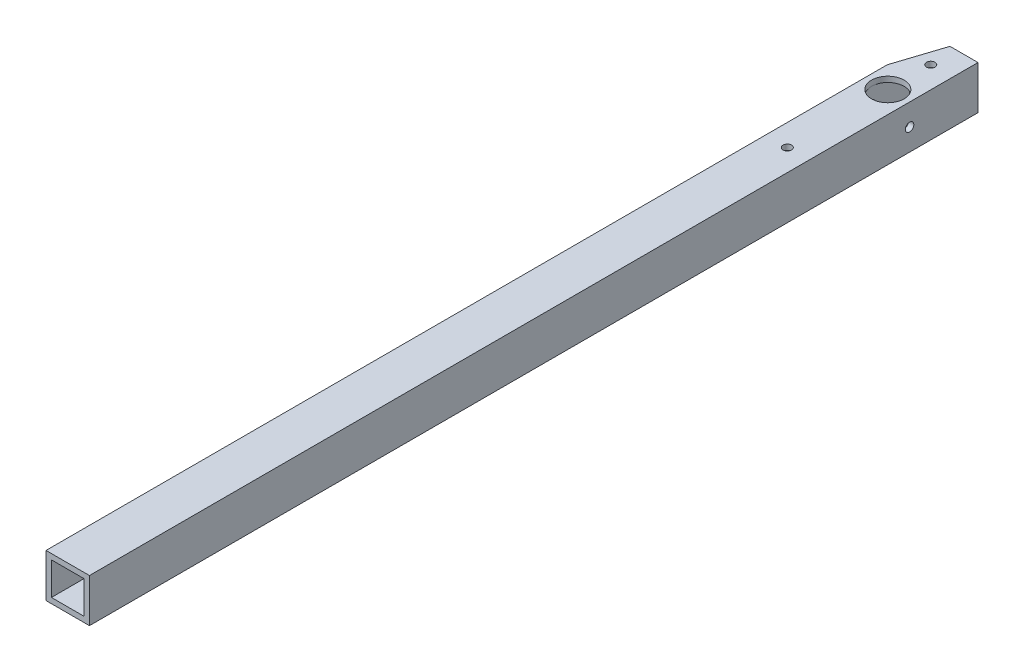
SolidWorks part; units mm, degrees
ref_plane "Front Plane" through (0, 0, 0) normal (0, 0, 1) x (1, 0, 0)
ref_plane "Top Plane" through (0, 0, 0) normal (0, 1, 0) x (1, 0, 0)
ref_plane "Right Plane" through (0, 0, 0) normal (1, 0, 0) x (0, 0, -1)
sketch "Sketch1" plane through (0, 0, 0) normal (0, 0, 1) x (1, 0, 0)
  line L0 (-9.525, 9.525) -> (9.525, 9.525)
  line L2 (-12.7, 12.7) -> (12.7, 12.7)
  line L3 (-12.7, 12.7) -> (-12.7, -12.7)
  line L4 (-12.7, -12.7) -> (12.7, -12.7)
  line L5 (12.7, 12.7) -> (12.7, -12.7)
  line L10 (9.525, 9.525) -> (9.525, -9.525)
  line L11 (-9.525, -9.525) -> (9.525, -9.525)
  line L12 (-9.525, 9.525) -> (-9.525, -9.525)
  point P12 (0, 12.7)
  point P14 (12.7, 0)
  dimension "Wall Thickness" = 3.175
  dimension "Outside Width" = 25.4
  dimension "Outside Height" = 25.4
  dimension "Inside Height" = 19.05
  dimension "Inside Width" = 19.05
sketch "Sketch2" plane through (0, 0, 0) normal (1, 0, 0) x (0, 0, -1)
  line L0 (266.7, 0) -> (-266.7, 0)
  point P4 (0, 0)
  point P7 (-266.7, 0)
  point P10 (266.7, 0)
  dimension "Length" = 533.4
sketch "Sketch3" plane through (0, 0, 0) normal (0, 0, 1) x (1, 0, 0)
  line L21 (12.7, 12.7) -> (-12.7, 12.7)
  line L22 (12.7, -12.7) -> (12.7, 12.7)
  line L23 (-12.7, -12.7) -> (12.7, -12.7)
  line L24 (-12.7, 12.7) -> (-12.7, -12.7)
  line L25 (12.7, 12.7) -> (-12.7, 12.7)
  line L26 (12.7, -12.7) -> (12.7, 12.7)
  line L27 (-12.7, -12.7) -> (12.7, -12.7)
  line L28 (-12.7, 12.7) -> (-12.7, -12.7)
  line L29 (9.525, 9.525) -> (-9.525, 9.525)
  line L30 (9.525, -9.525) -> (9.525, 9.525)
  line L31 (-9.525, -9.525) -> (9.525, -9.525)
  line L32 (-9.525, 9.525) -> (-9.525, -9.525)
  line L33 (9.525, 9.525) -> (-9.525, 9.525)
  line L34 (9.525, -9.525) -> (9.525, 9.525)
  line L35 (-9.525, -9.525) -> (9.525, -9.525)
  line L36 (-9.525, 9.525) -> (-9.525, -9.525)
  dimension "D1" = 0
  dimension "D2" = 0
extrude "Boss-Extrude1" add sketch "Sketch3" along normal up to vertex (266.7 mm away) and the other way up to vertex (266.7 mm away) up to point (0, 0, 266.7) other way up to point (0, 0, -266.7)
sketch "Drawing Reference" plane through (0, 0, 0) normal (1, 0, 0) x (0, 0, -1)
  line L0 (-266.7, 0) -> (266.7, 0) construction
  line L1 (0, -12.7) -> (0, 12.7) construction
  line L2 (-266.7, -12.7) -> (266.7, -12.7) construction
  line L5 (-266.7, 12.7) -> (266.7, 12.7) construction
  point P7 (-248.412, 0)
  point P8 (248.412, 0)
  dimension "D1" = 18.288
sketch "Sketch4" plane through (0, 12.7, 0) normal (0, 1, 0) x (1, 0, 0)
  line L1 (0, 266.7) -> (0, 212.725) construction
  line L7 (-12.7, 225.0135) -> (-12.7, 266.7)
  line L8 (-188.9197, -317.3351) -> (4.6184, 278.3139) construction
  line L10 (-12.7, -266.7) -> (-12.7, 266.7) construction
  line L11 (-12.7, 266.7) -> (12.7, 266.7)
  line L12 (12.7, 266.7) -> (12.7, 252.73)
  line L13 (12.7, -266.7) -> (12.7, 266.7) construction
  line L14 (12.7, 252.73) -> (-3.6943, 252.73)
  line L15 (-3.6943, 252.73) -> (-12.7, 225.0135)
  circle A0 centre (0, 212.725) radius 9.525
  dimension "D1" = 13.97
extrude "Cut-Extrude1" cut sketch "Sketch4" against normal blind 25.4
sketch "Sketch5" plane through (0, -12.7, 0) normal (0, -1, 0) x (1, 0, 0)
  circle A0 centre (0.3539, -181.928) radius 9.525
extrude "Cut-Extrude2" cut sketch "Sketch5" against normal blind 3.175
sketch "Sketch6" plane through (12.7, 0, 0) normal (1, 0, 0) x (0, 0, -1)
  line L0 (252.73, 0) -> (212.725, 0) construction
  line L1 (252.73, -12.7) -> (252.73, 12.7) construction
hole_wizard "#10 Clearance Hole1" positions "Sketch7" profile "Sketch8" hole size "#10" standard "ANSI Inch" end condition through all
sketch "Sketch7" plane through (12.7, 0, 0) normal (1, 0, 0) x (0, 0, -1)
  point P0 (212.725, 0)
sketch "Sketch8" plane through (12.7, 0, -212.725) normal (0, 1, 0) x (0, 0, -1)
  line L0 (0, 0) -> (0, 25.4)
  line L1 (0, 25.4) -> (2.4892, 25.4)
  line L2 (2.4892, 25.4) -> (2.4892, 0)
  line L5 (2.4892, 0) -> (0, 0)
  line L11 (0, -6.35) -> (0, 107.95) construction
  dimension "Thru Hole Dia." = 4.9784
  dimension "Thru Hole Depth" = 25.4
hole_wizard "#10 Clearance Hole2" positions "Sketch9" profile "Sketch10" hole size "#10" standard "ANSI Inch" end condition through all
sketch "Sketch9" plane through (0, 12.7, 0) normal (0, 1, 0) x (1, 0, 0)
  point P0 (0, 153.96)
  point P3 (0, 237.8065)
sketch "Sketch10" plane through (0, 12.7, -153.96) normal (1, 0, 0) x (0, 0, 1)
  line L0 (0, 0) -> (0, 25.4)
  line L1 (0, 25.4) -> (2.4892, 25.4)
  line L2 (2.4892, 25.4) -> (2.4892, 0)
  line L5 (2.4892, 0) -> (0, 0)
  line L11 (0, -6.35) -> (0, 107.95) construction
  dimension "Thru Hole Dia." = 4.9784
  dimension "Thru Hole Depth" = 25.4
equation "\"D1@Drawing Reference\"=\"Outside Width@Sketch1\" * 0.72"
